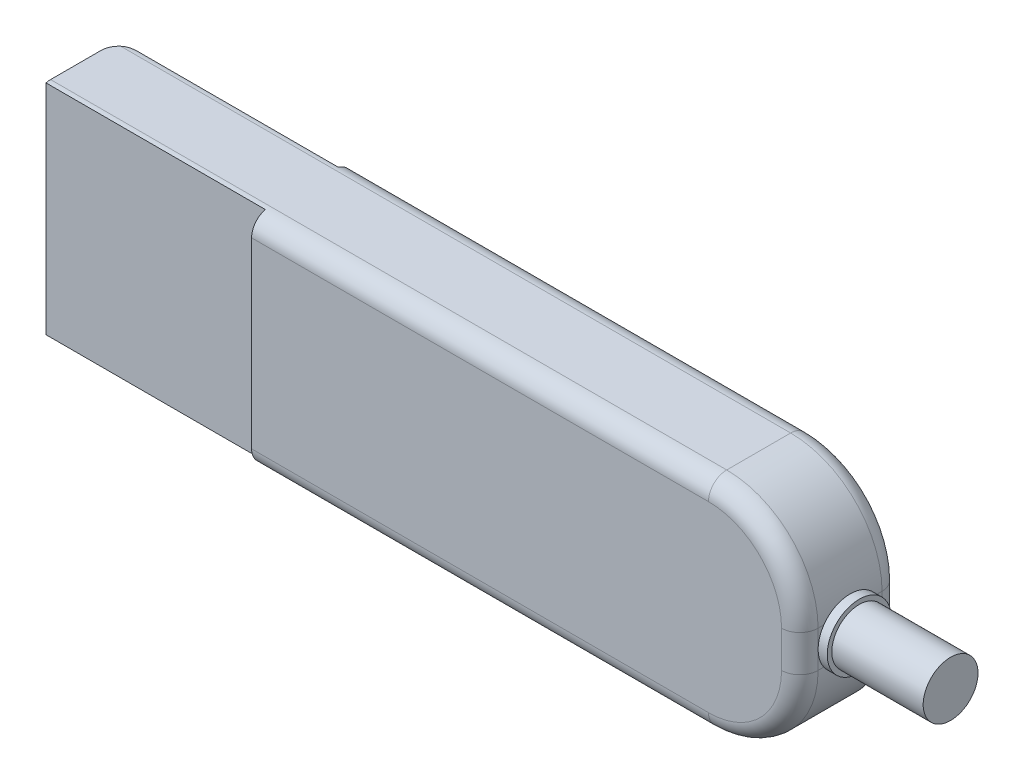
SolidWorks part; units mm, degrees
ref_plane "Plan de face" through (0, 0, 0) normal (0, 0, 1) x (1, 0, 0)
ref_plane "Plan de dessus" through (0, 0, 0) normal (0, 1, 0) x (1, 0, 0)
ref_plane "Plan de droite" through (0, 0, 0) normal (1, 0, 0) x (0, 0, -1)
sketch "Esquisse1" plane through (0, 0, 0) normal (0, 0, 1) x (1, 0, 0)
  line L1 (0, 0) -> (25, 0)
  line L2 (0, 0) -> (0, 12)
  line L3 (0, 12) -> (25, 12)
  line L4 (30, 5) -> (30, 7)
  line L5 (0, 12) -> (-13.747, 12)
  line L6 (0, 12) -> (0, 0)
  line L7 (0, 0) -> (-13.747, 0)
  line L8 (-13.747, 12) -> (-13.747, 0)
  arc A0 (25, 0) -> (30, 5) centre (25, 5) ccw
  arc A1 (25, 12) -> (30, 7) centre (25, 7) cw
  point P7 (30, 0)
  point P10 (30, 12)
  dimension "D3" = 5
  dimension "D1" = 12
  dimension "D2" = 30
  dimension "D4" = 12
  dimension "D5" = 0
extrude "Boss.-Extru.1" add sketch "Esquisse1" along normal blind 5.5 contours A1 L3 L2 L1 A0 L4 region at (14.5735, 6, 0)
ref_plane "Plan1" through (0, 0, 0.75) normal (0, 0, 1) x (1, 0, 0)
sketch "Esquisse6" plane through (0, 0, 0.75) normal (0, 0, 1) x (1, 0, 0)
  line L0 (0, -3.025) -> (0, 3.025) construction
  line L1 (0, 12) -> (-12, 12)
  line L2 (0, 12) -> (0, 0)
  line L3 (0, 0) -> (-12, 0)
  line L4 (-12, 12) -> (-12, 0)
  line L5 (0, 12) -> (25, 12) construction
  line L6 (3.025, 0) -> (-3.025, 0) construction
  dimension "D1" = 12
extrude "Boss.-Extru.4" add sketch "Esquisse6" along normal blind 4
sketch "Esquisse7" plane through (30, 0, 0) normal (1, 0, 0) x (0, 0, -1)
  line L0 (-5.5, 12) -> (0, 12) construction
  line L1 (-5.5, 5) -> (-5.5, 7) construction
  circle A0 centre (-2.75, 6) radius 1.75
  dimension "D1" = 3.5
  dimension "D2" = 6
  dimension "D3" = 2.75
extrude "Boss.-Extru.7" add sketch "Esquisse7" along normal blind 0.5
sketch "Esquisse8" plane through (30.5, 0, 0) normal (1, 0, 0) x (0, 0, -1)
  line L0 (-5.5, 5) -> (-5.5, 7) construction
  line L1 (-5.5, 12) -> (0, 12) construction
  circle A0 centre (-2.75, 6) radius 1.5
  point P2 (-5.5, 6)
  dimension "D1" = 3
  dimension "D2" = 2.75
  dimension "D3" = 6
extrude "Boss.-Extru.9" add sketch "Esquisse8" along normal blind 5
fillet "Congé1" radius 1 5 edges at (12.5, 0, 5.5) (28.5355, 1.4645, 5.5) (30, 6, 5.5) (28.5355, 10.5355, 5.5) (12.5, 12, 5.5)
fillet "Congé2" radius 1 1 edges at (-12, 6, 0.75)
fillet "Congé3" radius 1 5 edges at (12.5, 0, 0) (28.5355, 1.4645, 0) (30, 6, 0) (28.5355, 10.5355, 0) (12.5, 12, 0)
sketch "Esquisse9" plane through (-12, 0, 0) normal (-1, 0, 0) x (0, 0, 1)
  line L0 (4.5, 12) -> (1.75, 12) construction
  line L1 (2.25, 11.75) -> (4.25, 11.75)
  line L2 (2.25, 11.75) -> (2.25, 0.25)
  line L3 (2.25, 0.25) -> (4.25, 0.25)
  line L4 (4.25, 11.75) -> (4.25, 0.25)
  line L5 (4.75, 11.9682) -> (4.75, 0.0318) construction
  dimension "D1" = 11.5
  dimension "D2" = 2
  dimension "D3" = 0.25
  dimension "D4" = 0.5
extrude "Enlèv. mat.-Extru.1" cut sketch "Esquisse9" against normal blind 12
